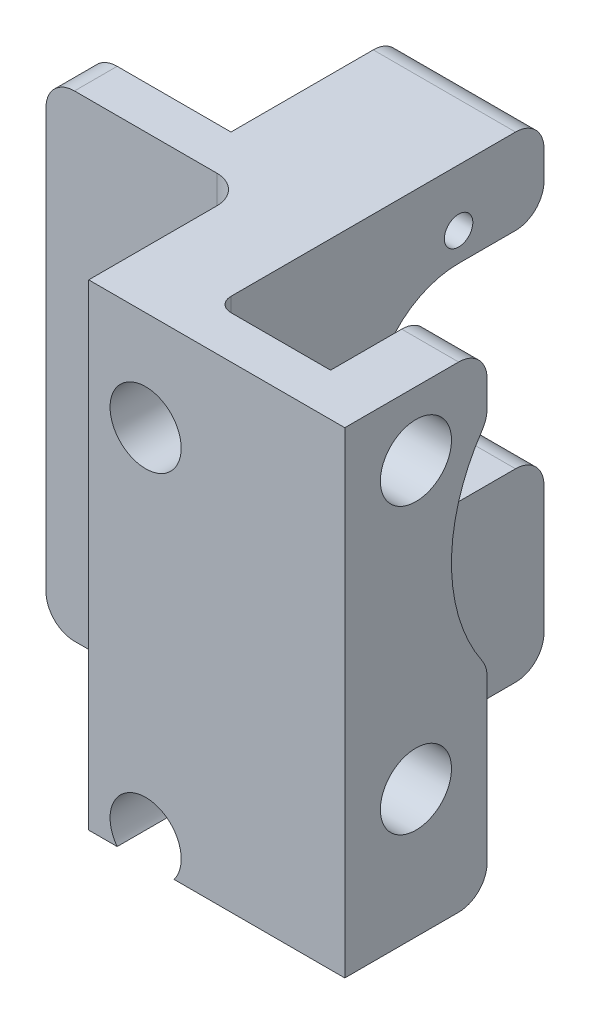
SolidWorks part; units mm, degrees
ref_plane "前视基准面" through (0, 0, 0) normal (0, 0, 1) x (1, 0, 0)
ref_plane "上视基准面" through (0, 0, 0) normal (0, 1, 0) x (1, 0, 0)
ref_plane "右视基准面" through (0, 0, 0) normal (1, 0, 0) x (0, 0, -1)
other "Configuration Table"
sketch "草图21" plane through (0, 0, 0) normal (1, 0, 0) x (0, 0, -1)
  line L0 (0, 12) -> (0, -21.5) construction
  line L3 (6, -21.5) -> (-9, -21.5)
  line L4 (-9, -21.5) -> (-9, 12) construction
  line L6 (-20, 12) -> (-20, -21.5)
  line L7 (-20, -21.5) -> (-9, -21.5)
  line L9 (0, 6) -> (6, 6)
  line L11 (0, -8.5) -> (6, -8.5)
  line L13 (6, 12) -> (6, 6)
  line L14 (6, -8.5) -> (6, -21.5)
  line L16 (-20, 12) -> (6, 12)
  circle A2 centre (0, 8) radius 1
  circle A3 centre (0, -19.5) radius 1
  arc A4 (-2.4451, -5.4792) -> (0, -8.5) centre (0, -6) ccw
  arc A5 (0, 6) -> (-2.4451, -5.4792) centre (0, 0) ccw
  dimension "D1" = 8
  dimension "D2" = 2.5
  dimension "D3" = 6
  dimension "D6" = 3
  dimension "D7" = 2
  dimension "D8" = 27.5
  dimension "D4" = 20
  dimension "D5" = 1
  dimension "D9" = 3
extrude "凸台-拉伸9" add sketch "草图21" along normal blind 6
sketch "草图22" plane through (6, 0, 0) normal (1, 0, 0) x (0, 0, -1)
  line L0 (-20, -21.5) -> (6, -21.5) construction
  line L1 (-20, 12) -> (-17, 12)
  line L2 (-20, 12) -> (-20, -21.5)
  line L3 (-20, -21.5) -> (-17, -21.5)
  line L4 (-17, 12) -> (-17, -21.5)
  line L5 (-20, 12) -> (-17, -21.5) construction
  line L6 (-20, -21.5) -> (-17, 12) construction
  point P4 (-18.5, -4.75)
  dimension "D1" = 3
extrude "凸台-拉伸10" add sketch "草图22" along normal blind 8
sketch "草图23" plane through (0, 0, 0) normal (-1, 0, 0) x (0, 0, 1)
  line L1 (6, 12) -> (9, 12)
  line L2 (6, 12) -> (6, -21.5)
  line L3 (6, -21.5) -> (9, -21.5)
  line L4 (9, 12) -> (9, -21.5)
  line L5 (6, 12) -> (9, -21.5) construction
  line L6 (6, -21.5) -> (9, 12) construction
  line L7 (20, -21.5) -> (-6, -21.5) construction
  line L8 (-6, 12) -> (17, 12) construction
  arc A0 (2.4451, -5.4792) -> (0, 6) centre (0, 0) ccw construction
  point P4 (7.5, -4.75)
  dimension "D1" = 3
extrude "凸台-拉伸11" add sketch "草图23" along normal blind 14
sketch "草图24" plane through (14, 0, 0) normal (1, 0, 0) x (0, 0, -1)
  line L0 (-17, -21.5) -> (6, -21.5) construction
  line L1 (-20, 12) -> (-10, 12)
  line L2 (-20, 12) -> (-20, -21.5)
  line L3 (-20, -21.5) -> (-10, -21.5)
  line L4 (-10, 12) -> (-10, 7.5)
  line L5 (-15, 12) -> (-15, -21.5) construction
  line L6 (-20, 12) -> (-20, -21.5) construction
  line L7 (-17, 12) -> (-20, 12) construction
  line L8 (-10, -7.5) -> (-10, -21.5)
  circle A0 centre (-15, 7.5) radius 2.5
  circle A1 centre (-15, -12.5) radius 2.5
  arc A2 (-10, 7.5) -> (-10, -7.5) centre (0, 0) ccw
  dimension "D2" = 5
  dimension "D3" = 20
  dimension "D4" = 2
  dimension "D6" = 7.5
  dimension "D7" = 25
  dimension "D8" = 1.7705
  dimension "D1" = 10
  dimension "D5" = 5
extrude "凸台-拉伸12" add sketch "草图24" along normal blind 4
sketch "草图25" plane through (0, 0, 20) normal (0, 0, 1) x (1, 0, 0)
  line L0 (4, 12) -> (4, -21.5) construction
  line L2 (18, -21.5) -> (0, -21.5) construction
  line L3 (0, 12) -> (0, -21.5) construction
  line L4 (18, 12) -> (0, 12) construction
  circle A0 centre (4, 5) radius 2.5
  circle A1 centre (4, -20) radius 2.5
  dimension "D1" = 25
  dimension "D3" = 5
  dimension "D4" = 5
  dimension "D2" = 4
extrude "切除-拉伸11" cut sketch "草图25" against normal blind 4
sketch "草图26" plane through (0, 0, 0) normal (-1, 0, 0) x (0, 0, 1)
  line L0 (6, 12) -> (6, -21.5) construction
  line L1 (-6, 12) -> (6, 12)
  line L2 (-6, 12) -> (-6, 6)
  line L3 (-6, 6) -> (6, 6)
  line L4 (6, 12) -> (6, 6)
  line L5 (-6, 12) -> (6, 6) construction
  line L6 (-6, 6) -> (6, 12) construction
  line L7 (0, 6) -> (-6, 6) construction
  line L8 (-6, -21.5) -> (6, -21.5)
  line L9 (-6, -21.5) -> (-6, -17.5)
  line L10 (-6, -17.5) -> (6, -17.5)
  line L11 (6, -21.5) -> (6, -17.5)
  line L12 (-6, -21.5) -> (6, -17.5) construction
  line L13 (-6, -17.5) -> (6, -21.5) construction
  circle A0 centre (0, -19.5) radius 1 construction
  circle A1 centre (0, 8) radius 1 construction
  circle A2 centre (0, -19.5) radius 1
  circle A3 centre (0, 8) radius 1
  point P4 (0, 9)
  point P12 (0, -19.5)
  dimension "D1" = 4
extrude "凸台-拉伸14" add sketch "草图26" along normal blind 4
fillet "圆角4" radius 2 11 edges at (-14, 12, 7.5) (-14, -21.5, 7.5) (0, -4.75, 9) (16, 12, 10) (1, 12, -6) (1, -21.5, -6) (3, -8.5, -6) (1, 6, -6) (16, 7.5, 10) (16, -7.5, 10) (16, -21.5, 10)
fillet "圆角5" radius 1 2 edges at (3, -5.4792, 2.4451) (6, -7.5, 17)
